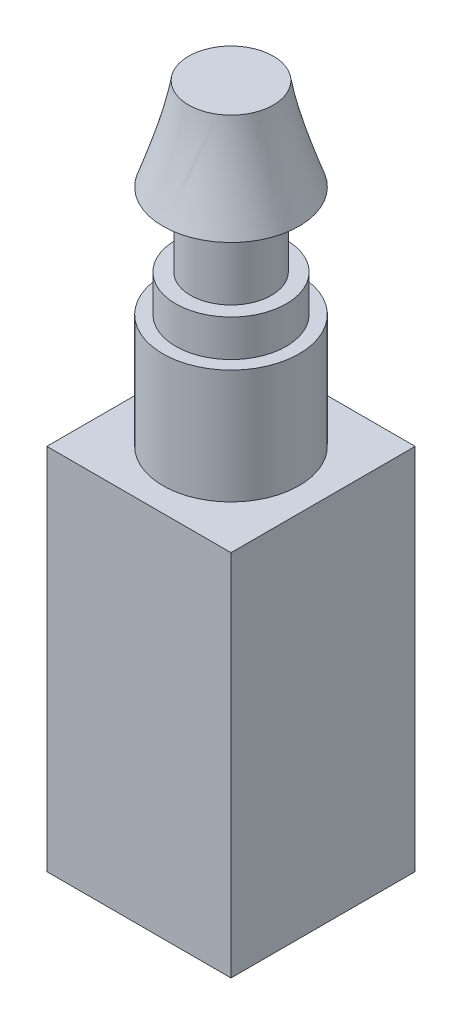
SolidWorks part; units mm, degrees
ref_plane "Front Plane" through (0, 0, 0) normal (0, 0, 1) x (1, 0, 0)
ref_plane "Top Plane" through (0, 0, 0) normal (0, 1, 0) x (1, 0, 0)
ref_plane "Right Plane" through (0, 0, 0) normal (1, 0, 0) x (0, 0, -1)
sketch "Sketch1" plane through (0, 0, 0) normal (0, 1, 0) x (1, 0, 0)
  circle A0 centre (0, 0) radius 1.85
  dimension "D1" = 3.7
extrude "Boss-Extrude1" add sketch "Sketch1" along normal blind 3.1
sketch "Sketch2" plane through (0, 3.1, 0) normal (0, 1, 0) x (1, 0, 0)
  circle A0 centre (0, 0) radius 1.5
  dimension "D1" = 3
extrude "Boss-Extrude2" add sketch "Sketch2" along normal blind 1
sketch "Sketch3" plane through (0, 4.1, 0) normal (0, 1, 0) x (1, 0, 0)
  circle A0 centre (0, 0) radius 1.1
  dimension "D1" = 2.2
extrude "Boss-Extrude3" add sketch "Sketch3" along normal blind 2
sketch "Sketch4" plane through (0, 6.1, 0) normal (0, 1, 0) x (1, 0, 0)
  circle A0 centre (0, 0) radius 1.85
  dimension "D1" = 3.7
ref_plane "Plane1" through (0, 8.6, 0) normal (0, 1, 0) x (1, 0, 0)
sketch "Sketch5" plane through (0, 8.6, 0) normal (0, 1, 0) x (1, 0, 0)
  circle A0 centre (0, 0) radius 1.15
  dimension "D1" = 2.3
loft "Loft1" add profiles "Sketch4", "Sketch5" connector at (0, 6.1, 1.85) connector at (0.6205, 8.6, 0.9683)
sketch "Sketch6" plane through (0, 0, 0) normal (0, -1, 0) x (1, 0, 0)
  line L1 (-2.5, 2.5) -> (2.5, 2.5)
  line L2 (-2.5, 2.5) -> (-2.5, -2.5)
  line L3 (-2.5, -2.5) -> (2.5, -2.5)
  line L4 (2.5, 2.5) -> (2.5, -2.5)
  line L5 (-2.5, 2.5) -> (2.5, -2.5) construction
  line L6 (-2.5, -2.5) -> (2.5, 2.5) construction
  point P0 (0, 0)
  dimension "D1" = 5
  dimension "D2" = 5
extrude "Boss-Extrude4" add sketch "Sketch6" along normal blind 10
